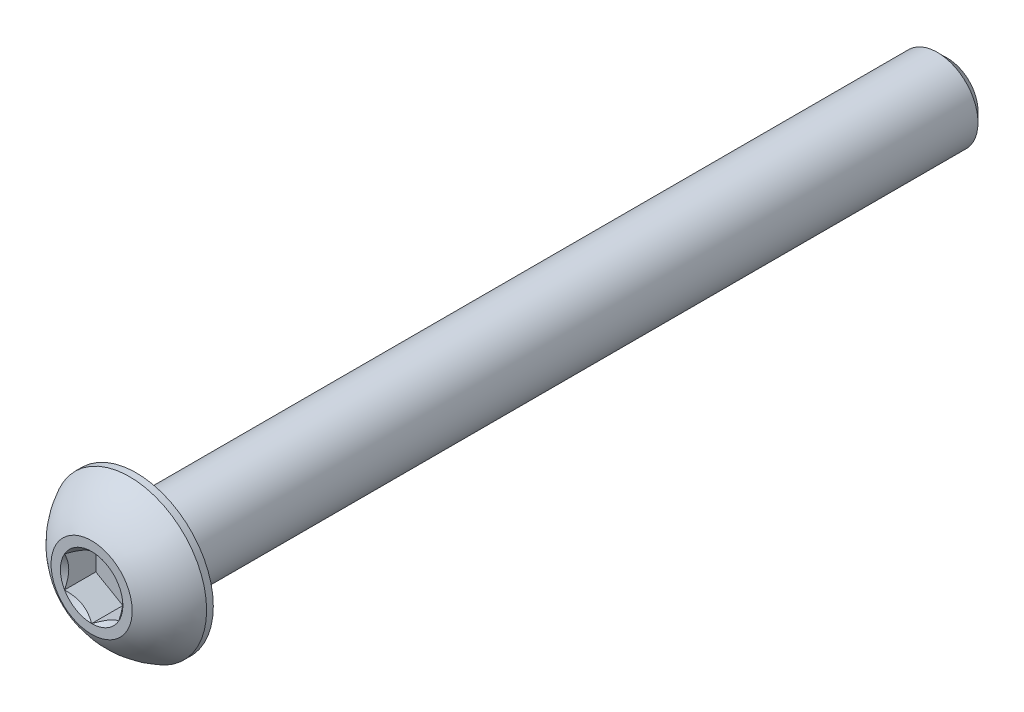
SolidWorks part; units mm, degrees
ref_plane "Front" through (0, 0, 0) normal (0, 0, 1) x (1, 0, 0)
ref_plane "Top" through (0, 0, 0) normal (0, 1, 0) x (1, 0, 0)
ref_plane "Right" through (0, 0, 0) normal (1, 0, 0) x (0, 0, -1)
sketch "Sketch1" plane through (0, 0, 0) normal (1, 0, 0) x (0, 0, -1)
  line L2 (1.65, 1.5) -> (31.65, 1.5)
  line L3 (31.65, 1.5) -> (31.65, 0)
  line L4 (31.65, 0) -> (1.65, 0)
  line L6 (1.4025, 2.85) -> (1.65, 2.85) construction
  line L7 (31.65, 1.5) -> (31.65, -1.5) construction
  line L8 (0, 0) -> (1.65, 0) construction
  line L9 (1.65, 2.85) -> (1.65, -2.85) construction
  line L11 (1.65, 1.5) -> (1.65, 0)
  line L13 (0, 1) -> (0, -1) construction
  line L14 (0, 1) -> (0, 1.5) construction
  line L15 (31.6187, 1.5541) -> (31.8687, 1.1211) construction
  line L16 (31.8687, 1.1211) -> (32.1187, 1.5541) construction
  line L17 (32.1187, 1.5541) -> (31.6187, 1.5541) construction
  line L18 (31.65, 1.5) -> (32.0875, 1.5) construction
  line L19 (31.8687, 1.5541) -> (31.8687, 1.5) construction
  line L20 (31.8687, 1.5) -> (31.8687, 1.1752) construction
  line L21 (31.8687, 1.1752) -> (31.8687, 1.1211) construction
  line L22 (31.8375, 1.1752) -> (31.9, 1.1752)
  line L23 (31.6344, 1.5271) -> (32.1031, 1.5271)
  line L24 (31.9, 1.1752) -> (32.1031, 1.5271)
  line L25 (31.8375, 1.1752) -> (31.6344, 1.5271)
  line L26 (31.275, 1.5) -> (31.65, 1.125)
  arc A3 (0, 1.5) -> (1.4025, 2.85) centre (2.7948, 0) cw construction
  point P29 (31.8687, 1.5271)
  point P30 (30.4, -1.5)
  dimension "D1" = 0.2475
  dimension "Pitch" = 0.5
  dimension "D3" = 0.0625
  dimension "D2" = 0.375
  dimension "D4" = 45
  dimension "D5" = 1.25
sketch "Sketch10" plane through (0, 0, 0) normal (1, 0, 0) x (0, 0, -1)
  line L0 (31.275, 1.5) -> (31.65, 1.125) construction
  line L1 (31.275, 1.5) -> (31.65, 1.125)
  line L4 (31.65, 1.5) -> (1.65, 1.5)
  line L5 (31.65, 0) -> (31.65, 1.5)
  line L6 (1.65, 0) -> (31.65, 0)
  line L7 (1.65, 1.5) -> (1.65, 0)
  line L8 (31.275, 1.5) -> (1.65, 1.5)
  line L9 (31.65, 0) -> (31.65, 1.125)
  line L10 (1.65, 0) -> (31.65, 0)
  line L11 (1.65, 1.5) -> (1.65, 0)
  dimension "D1" = 0
revolve "Revolve3" add sketch "Sketch10" angle 360 about L8
sketch "Sketch7" plane through (0, 0, 0) normal (1, 0, 0) x (0, 0, -1)
  line L6 (1.4025, 2.85) -> (1.65, 2.85) construction
  line L8 (0, 0) -> (1.65, 0) construction
  line L11 (1.65, 2.85) -> (1.65, -2.85) construction
  line L12 (1.4025, 2.85) -> (1.65, 2.85)
  line L13 (0, 0) -> (1.65, 0)
  line L14 (0, 1) -> (0, -1) construction
  line L15 (1.65, 2.85) -> (1.65, 0)
  line L16 (0, 1.5) -> (0, 0)
  arc A2 (1.4025, 2.85) -> (0, 1.5) centre (2.7948, 0) ccw construction
  arc A3 (1.4025, 2.85) -> (0, 1.5) centre (2.7948, 0) ccw
revolve "Revolve2" add sketch "Sketch7" angle 360 mid plane about L13
sketch "Sketch5" plane through (0, 0, 0) normal (0, 0, 1) x (1, 0, 0)
  line L1 (1, -0.5774) -> (1, 0.5774)
  line L2 (1, 0.5774) -> (0, 1.1547)
  line L3 (0, 1.1547) -> (-1, 0.5774)
  line L4 (-1, 0.5774) -> (-1, -0.5774)
  line L5 (-1, -0.5774) -> (0, -1.1547)
  line L6 (0, -1.1547) -> (1, -0.5774)
  circle A0 centre (0, 0) radius 1 construction
extrude "Cut-Extrude2" cut sketch "Sketch5" against normal blind 1.155
sketch "Sketch6" plane through (0, 0, 0) normal (0, 0, 1) x (1, 0, 0)
  circle A0 centre (0, 0) radius 1.1547
extrude "Cut-Extrude3" cut sketch "Sketch6" against normal blind 1.155 draft 45
sketch "Sketch9" [suppressed] plane through (0, 0, -1.65) normal (0, 0, -1) x (-1, 0, 0)
  circle A0 centre (0, 0) radius 1.5 construction
  circle A4 centre (0, 0) radius 1.5
split "Split1" [suppressed] bodies to split 113
sketch "Sketch11" [suppressed] plane through (0, 0, -31.65) normal (0, 0, -1) x (-1, 0, 0)
  circle A0 centre (0, 0) radius 1.5 construction
  circle A1 centre (0, 0) radius 1.5
curve "Helix/Spiral1" [suppressed] pitch 0.5 height 31.65 turns 63.3
sketch "Sketch12" [suppressed] plane through (0, 0, 0) normal (1, 0, 0) x (0, 0, -1)
  line L0 (31.8375, 1.1752) -> (31.9, 1.1752) construction
  line L1 (31.9, 1.1752) -> (32.1031, 1.5271) construction
  line L2 (31.6344, 1.5271) -> (32.1031, 1.5271) construction
  line L3 (31.8375, 1.1752) -> (31.6344, 1.5271) construction
  line L4 (31.8375, 1.1752) -> (31.9, 1.1752)
  line L5 (31.9, 1.1752) -> (32.1031, 1.5271)
  line L6 (31.6344, 1.5271) -> (32.1031, 1.5271)
  line L7 (31.8375, 1.1752) -> (31.6344, 1.5271)
sweep "Cut-Sweep2" [suppressed] cut profiles "Sketch12" path "Helix/Spiral1"
extrude "Boss-Extrude1" [suppressed] add sketch "Sketch9" along normal blind 10 draft 45
equation "\"D1@Cut-Extrude2\" = \"Head Ht@Sketch1\" * .7"
equation "\"D1@Sketch1\" = \"Head Ht@Sketch1\" * .15"
equation "\"D1@Cut-Extrude3\" = \"D1@Cut-Extrude2\""
equation "\"D3@Sketch1\" = \"Pitch@Sketch1\" / 8"
equation "\"D2@Sketch1\"=\"Pitch@Sketch1\"*0.75"
equation "\"D3@Helix/Spiral1\" = \"Lg@Sketch1\" + \"Head Ht@Sketch1\""
equation "\"D4@Helix/Spiral1\"=\"pitch@sketch1\""
equation "\"D5@Sketch1\"=\"Pitch@Sketch1\"*2.5"
